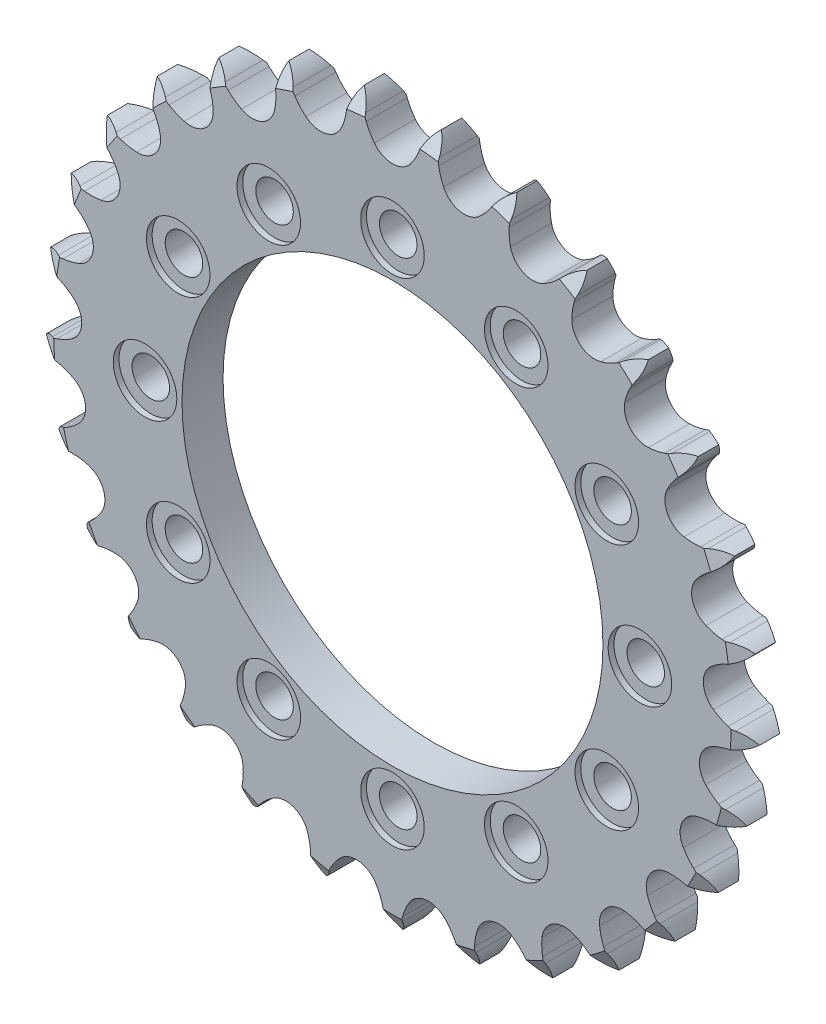
SolidWorks part; units mm, degrees
material "7075-T6 (SN)"
ref_plane "Front Plane" through (0, 0, 0) normal (0, 0, 1) x (1, 0, 0)
ref_plane "Top Plane" through (0, 0, 0) normal (0, 1, 0) x (1, 0, 0)
ref_plane "Right Plane" through (0, 0, 0) normal (1, 0, 0) x (0, 0, -1)
sketch "Work Sketch" plane through (0, 0, 0) normal (0, 0, 1) x (1, 0, 0)
  line L0 (0, 0) -> (0, 160.4542) construction
  line L1 (-112.0919, 58.7316) -> (87.2579, 58.7316) construction
  line L2 (5.0667, 120.8822) -> (5.0667, 112.9699) construction
  line L3 (-12.8497, 62.5592) -> (16.7256, 62.5592) construction
  line L4 (5.0667, 62.5592) -> (-6.0459, 54.1643) construction
  line L5 (5.0667, 62.5592) -> (-4.6207, 58.8405) construction
  line L6 (-4.6207, 58.8405) -> (-7.1024, 65.3054)
  line L7 (-11.5114, 57.5301) -> (-7.1525, 57.5301) construction
  line L8 (-11.0474, 124.7602) -> (-11.0474, 110.2345) construction
  line L9 (0, 0) -> (-4.6224, 42.5026) construction
  circle A0 centre (0, 0) radius 58.7316
  circle A1 centre (0, 58.7316) radius 4.0088
  arc A2 (-4.6207, 58.8405) -> (-3.1987, 56.3151) centre (5.0434, 62.6194) ccw
  circle A3 centre (-11.0474, 57.5301) radius 6.4694
  point P23 (-3.1987, 56.3151)
  dimension "D1" = 117.4631
  dimension "D8" = 10.3767
  dimension "D2" = 8.0177
  dimension "D3" = 5.0667
  dimension "D4" = 3.8276
  dimension "D5" = 37.069
  dimension "D6" = 16.069
  dimension "D7" = 10.3767
  dimension "D9" = 1.2015
  dimension "D10" = 11.0474
  dimension "D11" = 6.207
sketch "Teeth Sketch" plane through (0, 0, 0) normal (0, 0, 1) x (1, 0, 0)
  line L0 (5.0077, 59.8485) -> (4.6207, 58.8405)
  line L1 (-10.0593, 92.4935) -> (-6.4279, 59.1035) construction
  line L2 (0, 0) -> (-14.5837, 131.9519) construction
  line L3 (7.9751, 59.5258) -> (8.1363, 58.4582)
  line L4 (21623.8037, -198827.5914) -> (-21628.4261, 198870.094) construction
  line L5 (0, 146.3285) -> (0, 56.9858) construction
  line L6 (17.7563, 57.3728) -> (17.1617, 56.4715)
  line L7 (0, -200000) -> (0, 200160.4542) construction
  line L8 (20.5849, 56.4197) -> (20.5128, 55.3424)
  line L9 (-4.6207, 58.8405) -> (-7.1024, 65.3054) construction
  line L10 (42.3724, 42.5618) -> (41.8546, 41.6143)
  line L11 (-5.0077, 59.8485) -> (-4.6207, 58.8405)
  line L12 (29.6746, 52.2144) -> (28.9002, 51.462)
  line L13 (32.2322, 50.6755) -> (31.9302, 49.6389)
  line L14 (40.2054, 44.6145) -> (39.2873, 44.0462)
  line L15 (48.8562, 34.9284) -> (47.8374, 34.5708)
  line L16 (50.5312, 32.4579) -> (49.8219, 31.6439)
  line L17 (55.2225, 23.6092) -> (54.1507, 23.4789)
  line L18 (56.3273, 20.8363) -> (55.4596, 20.1938)
  line L19 (59.0067, 11.186) -> (57.932, 11.2892)
  line L20 (59.4896, 8.2405) -> (58.5041, 7.7995)
  line L21 (60.0319, -1.7602) -> (59.0044, -1.4284)
  line L22 (59.8703, -4.7407) -> (58.8129, -4.9595)
  line L23 (58.25, -14.6241) -> (57.3178, -14.0792)
  line L24 (57.4514, -17.5002) -> (56.3718, -17.4866)
  line L25 (53.7443, -26.8042) -> (52.9512, -26.0717)
  line L26 (52.3462, -29.4414) -> (51.2948, -29.196)
  line L27 (46.7257, -37.731) -> (46.1086, -36.8451)
  line L28 (44.7933, -40.006) -> (43.8192, -39.5403)
  line L29 (37.5222, -46.8935) -> (37.11, -45.8956)
  line L30 (35.146, -48.6999) -> (34.2948, -48.0357)
  line L31 (26.5643, -53.8634) -> (26.3761, -52.8002)
  line L32 (23.8553, -55.1167) -> (23.1667, -54.285)
  line L33 (14.3642, -58.3146) -> (14.409, -57.2358)
  line L34 (11.4491, -58.9563) -> (10.9554, -57.996)
  line L35 (1.4924, -60.0391) -> (1.7681, -58.9952)
  line L36 (-1.4924, -60.0391) -> (-1.7681, -58.9952)
  line L37 (-11.4491, -58.9563) -> (-10.9554, -57.996)
  line L38 (-14.3642, -58.3146) -> (-14.409, -57.2358)
  line L39 (-23.8553, -55.1167) -> (-23.1667, -54.285)
  line L40 (-26.5643, -53.8634) -> (-26.3761, -52.8002)
  line L41 (-35.146, -48.6999) -> (-34.2948, -48.0357)
  line L42 (-37.5222, -46.8935) -> (-37.11, -45.8956)
  line L43 (-44.7933, -40.006) -> (-43.8192, -39.5403)
  line L44 (-46.7257, -37.731) -> (-46.1086, -36.8451)
  line L45 (-52.3462, -29.4414) -> (-51.2948, -29.196)
  line L46 (-53.7443, -26.8042) -> (-52.9512, -26.0717)
  line L47 (-57.4514, -17.5002) -> (-56.3718, -17.4866)
  line L48 (-58.25, -14.6241) -> (-57.3178, -14.0792)
  line L49 (-59.8703, -4.7407) -> (-58.8129, -4.9595)
  line L50 (-60.0319, -1.7602) -> (-59.0044, -1.4284)
  line L51 (-59.4896, 8.2405) -> (-58.5041, 7.7995)
  line L52 (-59.0067, 11.186) -> (-57.932, 11.2892)
  line L53 (-56.3273, 20.8363) -> (-55.4596, 20.1938)
  line L54 (-55.2225, 23.6092) -> (-54.1507, 23.4789)
  line L55 (-50.5312, 32.4579) -> (-49.8219, 31.6439)
  line L56 (-48.8562, 34.9284) -> (-47.8374, 34.5708)
  line L57 (-42.3724, 42.5618) -> (-41.8546, 41.6143)
  line L58 (-40.2054, 44.6145) -> (-39.2873, 44.0462)
  line L59 (-32.2322, 50.6755) -> (-31.9302, 49.6389)
  line L60 (-29.6746, 52.2144) -> (-28.9002, 51.462)
  line L61 (-20.5849, 56.4197) -> (-20.5128, 55.3424)
  line L62 (-17.7563, 57.3728) -> (-17.1617, 56.4715)
  line L63 (-7.9751, 59.5258) -> (-8.1363, 58.4582)
  arc A0 (-6.9079, 62.5018) -> (-5.0077, 59.8485) centre (-11.0474, 57.5301) cw
  circle A1 centre (-11.0474, 57.5301) radius 6.4694 construction
  arc A2 (-3.1987, 56.3151) -> (-4.6207, 58.8405) centre (5.0434, 62.6194) cw
  arc A3 (-4.6207, 58.8405) -> (-3.1987, 56.3151) centre (5.0434, 62.6194) ccw construction
  circle A4 centre (0, 58.7316) radius 4.0088 construction
  arc A5 (-3.1987, 56.3151) -> (3.1987, 56.3151) centre (0, 58.7316) ccw
  arc A6 (3.1987, 56.3151) -> (4.6207, 58.8405) centre (-5.0434, 62.6194) ccw
  arc A7 (6.9079, 62.5018) -> (5.0077, 59.8485) centre (11.0474, 57.5301) ccw
  arc A8 (6.6897, 62.5255) -> (7.9751, 59.5258) centre (1.5782, 58.5599) cw
  arc A9 (8.9822, 55.6862) -> (8.1363, 58.4582) centre (18.3868, 60.0712) cw
  arc A10 (8.9822, 55.6862) -> (15.23, 54.3109) centre (12.6256, 57.3585) ccw
  arc A11 (15.23, 54.3109) -> (17.1617, 56.4715) centre (8.5358, 62.2396) ccw
  arc A12 (20.1824, 59.5555) -> (17.7563, 57.3728) centre (23.1563, 53.8102) ccw
  arc A13 (19.9744, 59.6256) -> (20.5849, 56.4197) centre (14.13, 56.8516) cw
  arc A14 (20.7431, 52.4533) -> (20.5128, 55.3424) centre (30.8705, 54.7141) cw
  arc A15 (20.7431, 52.4533) -> (26.5492, 49.7671) centre (24.6607, 53.3033) ccw
  arc A16 (26.5492, 49.7671) -> (28.9002, 51.462) centre (21.7159, 58.9495) ccw
  arc A17 (32.5132, 53.8245) -> (29.6746, 52.2144) centre (34.1826, 47.5742) ccw
  arc A18 (32.3251, 53.9377) -> (32.2322, 50.6755) centre (26.021, 52.4849) cw
  arc A19 (31.534, 46.7679) -> (31.9302, 49.6389) centre (41.9107, 46.7987) cw
  arc A20 (31.534, 46.7679) -> (36.6269, 42.8963) centre (35.5428, 46.7558) ccw
  arc A21 (36.6269, 42.8963) -> (39.2873, 44.0462) centre (33.8806, 52.903) ccw
  arc A22 (43.3238, 45.5768) -> (40.2054, 44.6145) centre (43.6105, 39.1137) ccw
  arc A23 (43.1644, 45.7277) -> (42.3724, 42.5618) centre (36.6954, 45.6641) cw
  arc A24 (40.8505, 38.8956) -> (41.8546, 41.6143) centre (50.9912, 36.695) cw
  arc A25 (40.8505, 38.8956) -> (44.9921, 34.0197) centre (44.763, 38.022) ccw
  arc A26 (44.9921, 34.0197) -> (47.8374, 34.5708) centre (44.4611, 44.3828) ccw
  arc A27 (52.1085, 35.1979) -> (48.8562, 34.9284) centre (50.9992, 28.8243) ccw
  arc A28 (51.9854, 35.3795) -> (50.5312, 32.4579) centre (45.6539, 36.7081) cw
  arc A29 (48.2568, 29.2046) -> (49.8219, 31.6439) centre (57.6874, 24.8755) cw
  arc A30 (48.2568, 29.2046) -> (51.2534, 23.5524) centre (51.8901, 27.5104) ccw
  arc A31 (51.2534, 23.5524) -> (54.1507, 23.4789) centre (52.9626, 33.7874) ccw
  arc A32 (58.4568, 23.1732) -> (55.2225, 23.6092) centre (56.0032, 17.1871) ccw
  arc A33 (58.3755, 23.3771) -> (56.3273, 20.8363) centre (52.4776, 26.0356) cw
  arc A34 (53.4067, 18.148) -> (55.4596, 20.1938) centre (61.6862, 11.8929) cw
  arc A35 (53.4067, 18.148) -> (55.1182, 11.9838) centre (56.5908, 15.7124) ccw
  arc A36 (55.1182, 11.9838) -> (57.932, 11.2892) centre (58.9877, 21.612) ccw
  arc A37 (62.0716, 10.0649) -> (59.0067, 11.186) centre (58.3886, 4.7463) ccw
  arc A38 (62.0361, 10.2815) -> (59.4896, 8.2405) centre (56.8476, 14.1458) cw
  arc A39 (56.0594, 6.2428) -> (58.5041, 7.7995) centre (62.8006, -1.6459) cw
  arc A40 (56.0594, 6.2428) -> (56.4057, -0.1452) centre (58.6454, 3.1797) ccw
  arc A41 (56.4057, -0.1452) -> (59.0044, -1.4284) centre (62.2545, 8.4262) ccw
  arc A42 (62.7841, -3.514) -> (60.0319, -1.7602) centre (58.0438, -7.9165) ccw
  arc A43 (62.796, -3.2948) -> (59.8703, -4.7407) centre (58.5595, 1.5945) cw
  arc A44 (56.0908, -5.9542) -> (58.8129, -4.9595) centre (60.9785, -15.1077) cw
  arc A45 (56.0908, -5.9542) -> (55.0558, -12.2673) centre (57.9579, -9.5017) ccw
  arc A46 (55.0558, -12.2673) -> (57.3178, -14.0792) centre (62.6104, -5.1537) ccw
  arc A47 (60.5608, -16.9285) -> (58.25, -14.6241) centre (54.985, -20.2092) ccw
  arc A48 (60.6196, -16.717) -> (57.4514, -17.5002) centre (57.5332, -11.0313) cw
  arc A49 (53.4994, -17.8729) -> (56.3718, -17.4866) centre (56.3052, -27.863) cw
  arc A50 (53.4994, -17.8729) -> (51.1315, -23.8159) centre (54.5603, -21.7388) ccw
  arc A51 (51.1315, -23.8159) -> (52.9512, -26.0717) centre (60.0387, -18.4926) ccw
  arc A52 (55.5058, -29.5515) -> (53.7443, -26.8042) centre (49.3551, -31.5568) ccw
  arc A53 (55.6086, -29.3576) -> (52.3462, -29.4414) centre (53.8167, -23.1414) cw
  arc A54 (48.4065, -28.9558) -> (51.2948, -29.196) centre (48.9991, -39.3156) cw
  arc A55 (48.4065, -28.9558) -> (44.8164, -34.2509) centre (48.6115, -32.9594) ccw
  arc A56 (44.8164, -34.2509) -> (46.1086, -36.8451) centre (54.6597, -30.9668) ccw
  arc A57 (47.8554, -40.7928) -> (46.7257, -37.731) centre (41.4174, -41.4289) ccw
  arc A58 (47.9975, -40.6255) -> (44.7933, -40.006) centre (47.5838, -34.1693) cw
  arc A59 (41.0501, -38.6848) -> (43.8192, -39.5403) centre (39.4018, -48.9297) cw
  arc A60 (41.0501, -38.6848) -> (36.4057, -43.0843) centre (40.3897, -42.6389) ccw
  arc A61 (36.4057, -43.0843) -> (37.11, -45.8956) centre (46.7248, -41.993) ccw
  arc A62 (37.9673, -50.1265) -> (37.5222, -46.8935) centre (31.5431, -49.3639) ccw
  arc A63 (38.1421, -49.9937) -> (35.146, -48.6999) centre (39.1259, -43.5996) cw
  arc A64 (31.7743, -46.6049) -> (34.2948, -48.0357) centre (27.9622, -56.256) cw
  arc A65 (31.7743, -46.6049) -> (26.2927, -49.9031) centre (30.2793, -50.3246) ccw
  arc A66 (26.2927, -49.9031) -> (26.3761, -52.8002) centre (36.6052, -51.0557) ccw
  arc A67 (26.304, -57.1165) -> (26.5643, -53.8634) centre (20.1939, -54.9906) ccw
  arc A68 (26.5032, -57.0243) -> (23.8553, -55.1167) centre (28.8385, -50.9911) cw
  arc A69 (21.0128, -52.3459) -> (23.1667, -54.285) centre (15.2151, -60.9518) cw
  arc A70 (21.0128, -52.3459) -> (14.9503, -54.3886) centre (18.7531, -55.6572) ccw
  arc A71 (14.9503, -54.3886) -> (14.409, -57.2358) centre (24.7739, -57.7311) ccw
  arc A72 (13.4106, -61.4357) -> (14.3642, -58.3146) centre (7.9004, -58.046) ccw
  arc A73 (13.625, -61.3885) -> (11.4491, -58.9563) centre (17.2027, -55.9984) cw
  arc A74 (9.2687, -55.6392) -> (10.9554, -57.996) centre (1.7565, -62.7976) cw
  arc A75 (9.2687, -55.6392) -> (2.9088, -56.3309) centre (6.35, -58.3873) ccw
  arc A76 (2.9088, -56.3309) -> (1.7681, -58.9952) centre (11.7842, -61.707) ccw
  arc A77 (-0.1098, -62.8823) -> (1.4924, -60.0391) centre (-4.7625, -58.3873) ccw
  arc A78 (0.1098, -62.8823) -> (-1.4924, -60.0391) centre (4.7625, -58.3873) cw
  arc A79 (-2.9088, -56.3309) -> (-1.7681, -58.9952) centre (-11.7842, -61.707) cw
  arc A80 (-2.9088, -56.3309) -> (-9.2687, -55.6392) centre (-6.35, -58.3873) ccw
  arc A81 (-9.2687, -55.6392) -> (-10.9554, -57.996) centre (-1.7565, -62.7976) ccw
  arc A82 (-13.625, -61.3885) -> (-11.4491, -58.9563) centre (-17.2027, -55.9984) ccw
  arc A83 (-13.4106, -61.4357) -> (-14.3642, -58.3146) centre (-7.9004, -58.046) cw
  arc A84 (-14.9503, -54.3886) -> (-14.409, -57.2358) centre (-24.7739, -57.7311) cw
  arc A85 (-14.9503, -54.3886) -> (-21.0128, -52.3459) centre (-18.7531, -55.6572) ccw
  arc A86 (-21.0128, -52.3459) -> (-23.1667, -54.285) centre (-15.2151, -60.9518) ccw
  arc A87 (-26.5032, -57.0243) -> (-23.8553, -55.1167) centre (-28.8385, -50.9911) ccw
  arc A88 (-26.304, -57.1165) -> (-26.5643, -53.8634) centre (-20.1939, -54.9906) cw
  arc A89 (-26.2927, -49.9031) -> (-26.3761, -52.8002) centre (-36.6052, -51.0557) cw
  arc A90 (-26.2927, -49.9031) -> (-31.7743, -46.6049) centre (-30.2793, -50.3246) ccw
  arc A91 (-31.7743, -46.6049) -> (-34.2948, -48.0357) centre (-27.9622, -56.256) ccw
  arc A92 (-38.1421, -49.9937) -> (-35.146, -48.6999) centre (-39.1259, -43.5996) ccw
  arc A93 (-37.9673, -50.1265) -> (-37.5222, -46.8935) centre (-31.5431, -49.3639) cw
  arc A94 (-36.4057, -43.0843) -> (-37.11, -45.8956) centre (-46.7248, -41.993) cw
  arc A95 (-36.4057, -43.0843) -> (-41.0501, -38.6848) centre (-40.3897, -42.6389) ccw
  arc A96 (-41.0501, -38.6848) -> (-43.8192, -39.5403) centre (-39.4018, -48.9297) ccw
  arc A97 (-47.9975, -40.6255) -> (-44.7933, -40.006) centre (-47.5838, -34.1693) ccw
  arc A98 (-47.8554, -40.7928) -> (-46.7257, -37.731) centre (-41.4174, -41.4289) cw
  arc A99 (-44.8164, -34.2509) -> (-46.1086, -36.8451) centre (-54.6597, -30.9668) cw
  arc A100 (-44.8164, -34.2509) -> (-48.4065, -28.9558) centre (-48.6115, -32.9594) ccw
  arc A101 (-48.4065, -28.9558) -> (-51.2948, -29.196) centre (-48.9991, -39.3156) ccw
  arc A102 (-55.6086, -29.3576) -> (-52.3462, -29.4414) centre (-53.8167, -23.1414) ccw
  arc A103 (-55.5058, -29.5515) -> (-53.7443, -26.8042) centre (-49.3551, -31.5568) cw
  arc A104 (-51.1315, -23.8159) -> (-52.9512, -26.0717) centre (-60.0387, -18.4926) cw
  arc A105 (-51.1315, -23.8159) -> (-53.4994, -17.8729) centre (-54.5603, -21.7388) ccw
  arc A106 (-53.4994, -17.8729) -> (-56.3718, -17.4866) centre (-56.3052, -27.863) ccw
  arc A107 (-60.6196, -16.717) -> (-57.4514, -17.5002) centre (-57.5332, -11.0313) ccw
  arc A108 (-60.5608, -16.9285) -> (-58.25, -14.6241) centre (-54.985, -20.2092) cw
  arc A109 (-55.0558, -12.2673) -> (-57.3178, -14.0792) centre (-62.6104, -5.1537) cw
  arc A110 (-55.0558, -12.2673) -> (-56.0908, -5.9542) centre (-57.9579, -9.5017) ccw
  arc A111 (-56.0908, -5.9542) -> (-58.8129, -4.9595) centre (-60.9785, -15.1077) ccw
  arc A112 (-62.796, -3.2948) -> (-59.8703, -4.7407) centre (-58.5595, 1.5945) ccw
  arc A113 (-62.7841, -3.514) -> (-60.0319, -1.7602) centre (-58.0438, -7.9165) cw
  arc A114 (-56.4057, -0.1452) -> (-59.0044, -1.4284) centre (-62.2545, 8.4262) cw
  arc A115 (-56.4057, -0.1452) -> (-56.0594, 6.2428) centre (-58.6454, 3.1797) ccw
  arc A116 (-56.0594, 6.2428) -> (-58.5041, 7.7995) centre (-62.8006, -1.6459) ccw
  arc A117 (-62.0361, 10.2815) -> (-59.4896, 8.2405) centre (-56.8476, 14.1458) ccw
  arc A118 (-62.0716, 10.0649) -> (-59.0067, 11.186) centre (-58.3886, 4.7463) cw
  arc A119 (-55.1182, 11.9838) -> (-57.932, 11.2892) centre (-58.9877, 21.612) cw
  arc A120 (-55.1182, 11.9838) -> (-53.4067, 18.148) centre (-56.5908, 15.7124) ccw
  arc A121 (-53.4067, 18.148) -> (-55.4596, 20.1938) centre (-61.6862, 11.8929) ccw
  arc A122 (-58.3755, 23.3771) -> (-56.3273, 20.8363) centre (-52.4776, 26.0356) ccw
  arc A123 (-58.4568, 23.1732) -> (-55.2225, 23.6092) centre (-56.0032, 17.1871) cw
  arc A124 (-51.2534, 23.5524) -> (-54.1507, 23.4789) centre (-52.9626, 33.7874) cw
  arc A125 (-51.2534, 23.5524) -> (-48.2568, 29.2046) centre (-51.8901, 27.5104) ccw
  arc A126 (-48.2568, 29.2046) -> (-49.8219, 31.6439) centre (-57.6874, 24.8755) ccw
  arc A127 (-51.9854, 35.3795) -> (-50.5312, 32.4579) centre (-45.6539, 36.7081) ccw
  arc A128 (-52.1085, 35.1979) -> (-48.8562, 34.9284) centre (-50.9992, 28.8243) cw
  arc A129 (-44.9921, 34.0197) -> (-47.8374, 34.5708) centre (-44.4611, 44.3828) cw
  arc A130 (-44.9921, 34.0197) -> (-40.8505, 38.8956) centre (-44.763, 38.022) ccw
  arc A131 (-40.8505, 38.8956) -> (-41.8546, 41.6143) centre (-50.9912, 36.695) ccw
  arc A132 (-43.1644, 45.7277) -> (-42.3724, 42.5618) centre (-36.6954, 45.6641) ccw
  arc A133 (-43.3238, 45.5768) -> (-40.2054, 44.6145) centre (-43.6105, 39.1137) cw
  arc A134 (-36.6269, 42.8963) -> (-39.2873, 44.0462) centre (-33.8806, 52.903) cw
  arc A135 (-36.6269, 42.8963) -> (-31.534, 46.7679) centre (-35.5428, 46.7558) ccw
  arc A136 (-31.534, 46.7679) -> (-31.9302, 49.6389) centre (-41.9107, 46.7987) ccw
  arc A137 (-32.3251, 53.9377) -> (-32.2322, 50.6755) centre (-26.021, 52.4849) ccw
  arc A138 (-32.5132, 53.8245) -> (-29.6746, 52.2144) centre (-34.1826, 47.5742) cw
  arc A139 (-26.5492, 49.7671) -> (-28.9002, 51.462) centre (-21.7159, 58.9495) cw
  arc A140 (-26.5492, 49.7671) -> (-20.7431, 52.4533) centre (-24.6607, 53.3033) ccw
  arc A141 (-20.7431, 52.4533) -> (-20.5128, 55.3424) centre (-30.8705, 54.7141) ccw
  arc A142 (-19.9744, 59.6256) -> (-20.5849, 56.4197) centre (-14.13, 56.8516) ccw
  arc A143 (-20.1824, 59.5555) -> (-17.7563, 57.3728) centre (-23.1563, 53.8102) cw
  arc A144 (-15.23, 54.3109) -> (-17.1617, 56.4715) centre (-8.5358, 62.2396) cw
  arc A145 (-15.23, 54.3109) -> (-8.9822, 55.6862) centre (-12.6256, 57.3585) ccw
  arc A146 (-8.9822, 55.6862) -> (-8.1363, 58.4582) centre (-18.3868, 60.0712) ccw
  arc A147 (-6.6897, 62.5255) -> (-7.9751, 59.5258) centre (-1.5782, 58.5599) ccw
  point P77 (0, 0)
  dimension "D1" = 6.207
  dimension "D2" = 6.307
  dimension "D3" = 29
extrude "Extrusion" add sketch "Teeth Sketch" along normal blind 7.2136 contours A0 region at (0, 0, 0)
ref_axis "Axis2" through (0, 0, 38.9715) along (0, 0, -1)
hole_wizard "M6 Clearance Hole1" positions "Sketch6" profile "Sketch7" hole size "M6" standard "ANSI Metric"
sketch "Sketch6" plane through (0, 0, 0) normal (0, 0, -1) x (-1, 0, 0)
  circle A0 centre (0, 0) radius 43.5
  point P0 (0, 43.5)
  dimension "D1" = 87
sketch "Sketch7" plane through (0, 43.5, 0) normal (1, 0, 0) x (0, 1, 0)
  line L0 (0, 0) -> (0, 19.2548)
  line L1 (0, 19.2548) -> (3.3, 17.272)
  line L2 (3.3, 17.272) -> (3.3, 0)
  line L5 (3.3, 0) -> (0, 0)
  line L10 (0, 19.2548) -> (-3.3, 17.272) construction
  line L11 (0, -6.35) -> (0, 107.95) construction
  dimension "Hole Dia." = 6.6
  dimension "Hole Depth" = 17.272
  dimension "Drill Angle" = 118
pattern_circular "CirPattern1" count 12 over 360 about axis through (0, 0, 38.9715) along (0, 0, -1) of "M6 Clearance Hole1"
sketch "Sketch8" plane through (0, 0, 0) normal (0, 0, -1) x (-1, 0, 0)
  circle A0 centre (0, 0) radius 37
  dimension "D1" = 74
extrude "Cut-Extrude1" cut sketch "Sketch8" against normal through all both and the other way through all
ref_plane "Sprocket Center Plane" through (0, 0, 3.6068) normal (0, 0, 1) x (1, 0, 0)
sketch "Pitch Circle" plane through (0, 0, 3.6068) normal (0, 0, -1) x (-1, 0, 0)
  circle A0 centre (0, 0) radius 58.7316 construction
  dimension "D1" = 117.4631
ref_plane "Center Plane" through (0, 0, 3.6068) normal (0, 0, 1) x (1, 0, 0)
ref_axis "Axis1" through (0, 0, 7.2136) along (0, 0, -1)
sketch "Sketch5" plane through (0, 0, 0) normal (1, 0, 0) x (0, 0, -1)
  line L0 (-1.8288, -62.7658) -> (-5.3848, -62.7658)
  line L1 (-7.2136, -16.7916) -> (0, -16.7916) construction
  line L2 (-5.3848, -62.7658) -> (-5.3848, -59.5722)
  line L3 (-5.3848, -59.5722) -> (-7.2136, -59.5722)
  line L4 (-7.2136, -59.5722) -> (-5.3848, -62.7658)
  line L5 (-7.2136, -59.5722) -> (-7.2136, -62.7658)
  line L6 (-7.2136, -62.7658) -> (-5.3848, -62.7658)
  line L7 (-7.2136, -62.7658) -> (0, -62.7658) construction
  dimension "D1" = 3.556
  dimension "D2" = 3.1936
  dimension "D3" = 1.8288
revolve "Cut-Revolve1" cut sketch "Sketch5" angle 360 about axis through (0, 0, 7.2136) along (0, 0, -1) region at (0, -61.7013, 6.604)
mirror "Mirror1" about plane through (0, 0, 3.6068) normal (0, 0, 1) of "Cut-Revolve1"
sketch "Sketch10" plane through (0, 0, 0) normal (0, 0, 1) x (1, 0, 0)
  circle A0 centre (-43.5, 0) radius 5.588
  dimension "D1" = 11.176
extrude "Cut-Extrude2" cut sketch "Sketch10" against normal blind 1.016 from surface starting at face at (-37, 0, 7.2136)
pattern_circular "CirPattern2" count 12 over 360 about axis through (0, 0, 38.9715) along (0, 0, -1) of "Cut-Extrude2"
ref_plane "Half Plane" through (0, 0, 3.6068) normal (0, 0, 1) x (1, 0, 0)
sketch "Motor Shaft Sprocket Dimensions" plane through (0, 0, 3.6068) normal (0, 0, 1) x (1, 0, 0)
  line L0 (0, 0) -> (-177.8, 0)
  line L1 (-177.8, 0) -> (-177.8, 23.6982)
  line L2 (-178.9676, 51.1816) -> (-2.4928, 58.6786)
  line L3 (-186.1252, -2.52) -> (-17.7748, -55.9773)
  line L4 (-2.4928, 58.6786) -> (0, 0)
  line L5 (0, 0) -> (-17.7748, -55.9773)
  circle A0 centre (-177.8, 23.6982) radius 27.5082
  circle A1 centre (0, 0) radius 58.7316 construction
  dimension "D3" = 55.0164
  dimension "D1" = 177.8
  dimension "D2" = 23.6982
  dimension "D4" = 200.049
sketch "Sketch11" plane through (0, 0, 0) normal (0, 0, 1) x (1, 0, 0)
  line L0 (-167.2094, -55.7997) -> (-36.0913, 46.3337)
  line L1 (-145.9214, -98.8914) -> (14.8674, -56.8186)
  circle A2 centre (-152.1323, -75.1555) radius 24.535
  circle A3 centre (0, 0) radius 58.7316
  dimension "D2" = 117.4631
  dimension "D3" = 49.07
  dimension "D1" = 169.6838
equation "\"P\"= 0.500'//Chain Pitch"
equation "\"N\"= 29'//Number of Teeth"
equation "\"Dr\"= 5 / 16'//Roller Diameter"
equation "\"Ds\"= 1.0005 * \"Dr\" + 0.003'Seating Curve DIameter"
equation "\"R\"= \"Ds\" / 2"
equation "\"A\"= 35 + 60 / \"N\""
equation "\"B\"= 18 - 56 / \"N\""
equation "\"ac\"= 0.8 * \"Dr\""
equation "\"M\"= 0.8 * \"Dr\" * cos ( 35 + 60 / \"N\" )"
equation "\"T\"= 0.8 * \"Dr\" * sin ( 35 + 60 / \"N\" )"
equation "\"E\"= 1.3025 * \"Dr\" + 0.0015"
equation "\"Chordal Length of Arc xy\"= ( 2.605 * \"Dr\" + 0.003 ) * sin ( 9 - 28 / \"N\" )"
equation "\"yz\"= \"Dr\" * ( 1.4 * sin ( 17 - 64 / \"N\" ) - 0.8 * sin ( 18 - 56 / \"N\" ) )"
equation "\"ab\"= 1.4 * \"Dr\""
equation "\"W\"= 1.4 * \"Dr\" * cos ( 180 / \"N\" )"
equation "\"V\"= 1.4 * \"Dr\" * sin ( 180 / \"N\" )"
equation "\"F\"= \"Dr\" * ( 0.8 * cos ( 18 - 56 / \"N\" ) + 1.4 * cos ( 17 - 64 / \"N\" ) - 1.3025 )"
equation "\"H\"= sqr ( \"F\" ^ 2 - ( 1.4 * \"Dr\" - \"P\" / 2 ) ^ 2 )"
equation "\"S\"= \"P\" / 2 * cos ( 180 / \"N\" ) + \"H\" * sin ( 180 / \"N\" )"
equation "\"PD\"= \"P\" / ( sin ( 180 / \"N\" ) )"
equation "\"D1@Work Sketch\" = \"PD\""
equation "\"D3@Work Sketch\" = \"M\""
equation "\"D4@Work Sketch\" = \"T\""
equation "\"D5@Work Sketch\" = \"A\""
equation "\"D6@Work Sketch\" = \"B\""
equation "\"D7@Work Sketch\" = \"E\""
equation "\"D8@Work Sketch\" = \"E\""
equation "\"D9@Work Sketch\" = \"V\""
equation "\"D10@Work Sketch\" = \"W\""
equation "\"D2@Work Sketch\" = \"R\" * 2"
equation "\"D11@Work Sketch\" = 180 / \"N\""
equation "\"D2@Teeth Sketch\" = 180 / \"N\" + 0.1"
equation "\"D3@Teeth Sketch\" = \"N\""
equation "\"Edge Thickness\"=0.5"
equation "\"D1@Pitch Circle\"=\"PD\""
equation "\"ST\"= 0.284'//Sprocket Thickness"
